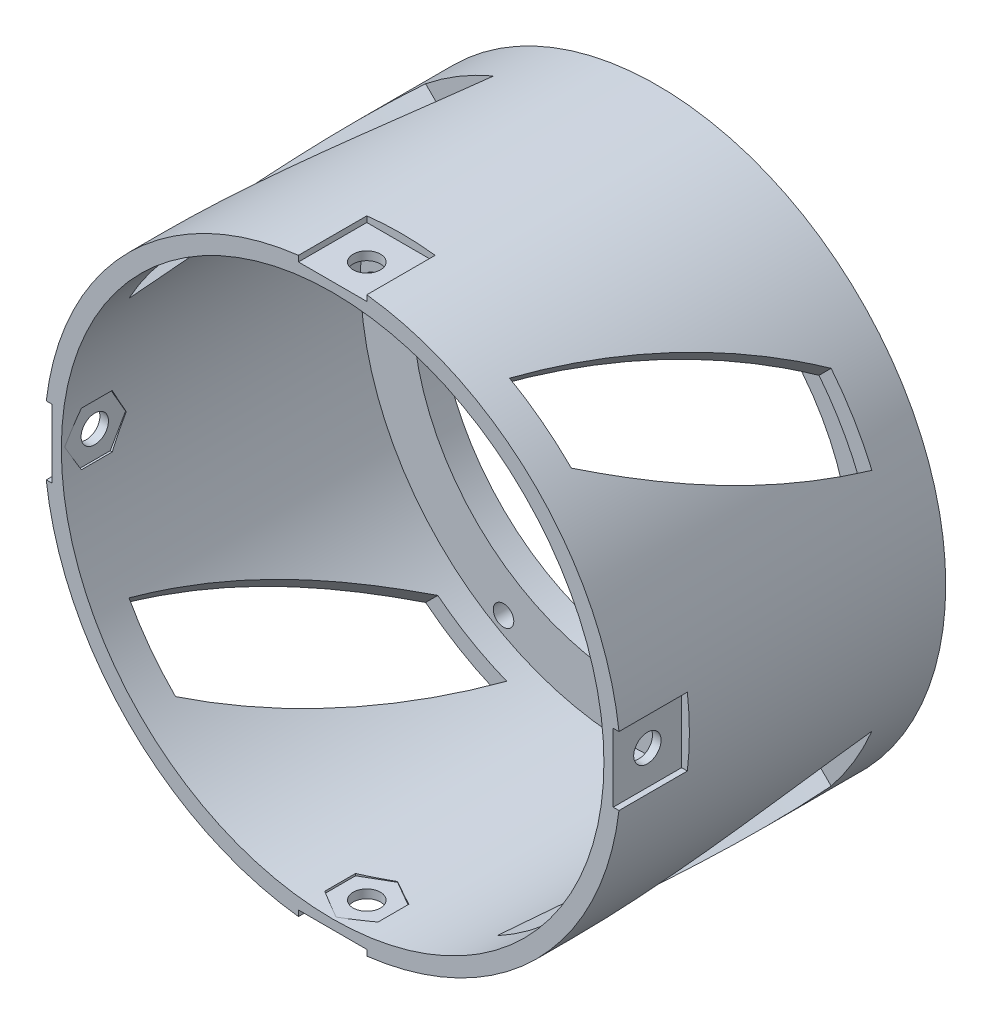
SolidWorks part; units mm, degrees
ref_plane "Front Plane" through (0, 0, 0) normal (0, 0, 1) x (1, 0, 0)
ref_plane "Top Plane" through (0, 0, 0) normal (0, 1, 0) x (1, 0, 0)
ref_plane "Right Plane" through (0, 0, 0) normal (1, 0, 0) x (0, 0, -1)
sketch "Sketch2" plane through (0, 0, 0) normal (0, 0, 1) x (1, 0, 0)
  circle A0 centre (0, 0) radius 42.8622
  circle A1 centre (0, 0) radius 32.5624
  circle A2 centre (-19.05, 32.9956) radius 1.524
  circle A3 centre (-38.1, 0) radius 1.524 construction
  circle A4 centre (-19.05, -32.9956) radius 1.524 construction
  circle A5 centre (19.05, -32.9956) radius 1.524 construction
  circle A6 centre (38.1, 0) radius 1.524 construction
  circle A7 centre (19.05, 32.9956) radius 1.524 construction
  circle A8 centre (-38.1, 0) radius 1.524
  circle A9 centre (-19.05, -32.9956) radius 1.524
  circle A10 centre (19.05, -32.9956) radius 1.524
  circle A11 centre (38.1, 0) radius 1.524
  circle A12 centre (19.05, 32.9956) radius 1.524
extrude "Boss-Extrude1" add sketch "Sketch2" along normal blind 3.81
sketch "Sketch3" plane through (0, 0, 3.81) normal (0, 0, 1) x (1, 0, 0)
  circle A1 centre (0, 0) radius 42.8622 construction
  circle A2 centre (0, 0) radius 40.3222
  circle A3 centre (0, 0) radius 40.3222
  circle A4 centre (0, 0) radius 42.8622
  dimension "D1" = 2.54
extrude "Boss-Extrude2" add sketch "Sketch3" along normal blind 44.45
sketch "Sketch7" plane through (0, 0, 48.26) normal (0, 0, 1) x (1, 0, 0)
  line L0 (-13.7134, 0) -> (50.6296, 0) construction
  line L1 (0, 9.0322) -> (0, -9.5161) construction
  line L2 (41.6999, -5.08) -> (41.6999, 5.08)
  line L3 (41.6999, 5.08) -> (44.3742, 5.08)
  line L4 (44.3742, 5.08) -> (44.3742, -5.08)
  line L5 (41.6999, -5.08) -> (44.3742, -5.08)
  line L6 (5.08, -44.3742) -> (-5.08, -44.3742)
  line L7 (-5.08, -41.6999) -> (-5.08, -44.3742)
  line L8 (-5.08, -41.6999) -> (5.08, -41.6999)
  line L9 (5.08, -41.6999) -> (5.08, -44.3742)
  line L10 (-44.3742, -5.08) -> (-44.3742, 5.08)
  line L11 (-41.6999, 5.08) -> (-44.3742, 5.08)
  line L12 (-41.6999, 5.08) -> (-41.6999, -5.08)
  line L13 (-41.6999, -5.08) -> (-44.3742, -5.08)
  line L14 (-5.08, 44.3742) -> (5.08, 44.3742)
  line L15 (5.08, 41.6999) -> (5.08, 44.3742)
  line L16 (5.08, 41.6999) -> (-5.08, 41.6999)
  line L17 (-5.08, 41.6999) -> (-5.08, 44.3742)
  point P10 (44.3742, 0)
  point P11 (41.6999, 0)
  point P26 (0, 0)
  dimension "D1" = 5.08
  dimension "D2" = 4
extrude "Cut-Extrude2" cut sketch "Sketch7" against normal blind 10.16
ref_plane "Plane1" through (40.4299, 0, 0) normal (1, 0, 0) x (0, 0, -1)
sketch "Sketch8" plane through (40.4299, 0, 0) normal (1, 0, 0) x (0, 0, -1)
  line L1 (-38.6046, 0) -> (-40.8923, 3.9624)
  line L2 (-40.8923, 3.9624) -> (-45.4677, 3.9624)
  line L3 (-45.4677, 3.9624) -> (-47.7554, 0)
  line L4 (-47.7554, 0) -> (-45.4677, -3.9624)
  line L5 (-45.4677, -3.9624) -> (-40.8923, -3.9624)
  line L6 (-40.8923, -3.9624) -> (-38.6046, 0)
  circle A0 centre (-43.18, 0) radius 3.9624 construction
  dimension "D1" = 7.9248
extrude "Cut-Extrude3" cut sketch "Sketch8" against normal blind 10.16
sketch "Sketch9" plane through (41.6999, 0, 0) normal (1, 0, 0) x (0, 0, -1)
  circle A0 centre (-43.18, 0) radius 2.032
  dimension "D1" = 4.064
extrude "Cut-Extrude4" cut sketch "Sketch9" against normal blind 10.16
pattern_circular "CirPattern2" count 4 every 90 about axis through (0, 0, 48.26) along (0, 0, 1) of "Cut-Extrude3", "Cut-Extrude4"
ref_axis "Axis2" through (0, 0, -2.413) along (0, 0, 1)
ref_plane "Plane2" through (0, 0, 0) normal (0.7071, 0.7071, 0) x (0, 0, 1)
sketch "Sketch10" plane through (0, 0, 0) normal (0.7071, 0.7071, 0) x (0, 0, 1)
  line L0 (7.5479, 16.0219) -> (7.5479, 4.5919)
  line L1 (43.1079, -11.4101) -> (43.1079, 0.0199)
  line L2 (7.5479, 2.4633) -> (43.1079, 2.4633) construction
  spline S0 degree 2 poles (7.5479, 4.5919) (23.6325, -7.2286) (43.1079, -11.4101) knots 0 0 0 1 1 1
  spline S1 degree 2 poles (7.5479, 16.0219) (26.8798, 11.5317) (43.1079, 0.0199) knots 0 0 0 1 1 1
  dimension "D1" = 11.43
  dimension "D2" = 11.43
  dimension "D3" = 35.56
  dimension "D4" = 4.572
extrude "Cut-Extrude5" cut sketch "Sketch10" against normal through all both and the other way through all
pattern_circular "CirPattern3" count 2 every 90 about axis through (0, 0, 48.26) along (0, 0, 1) of "Cut-Extrude5"
